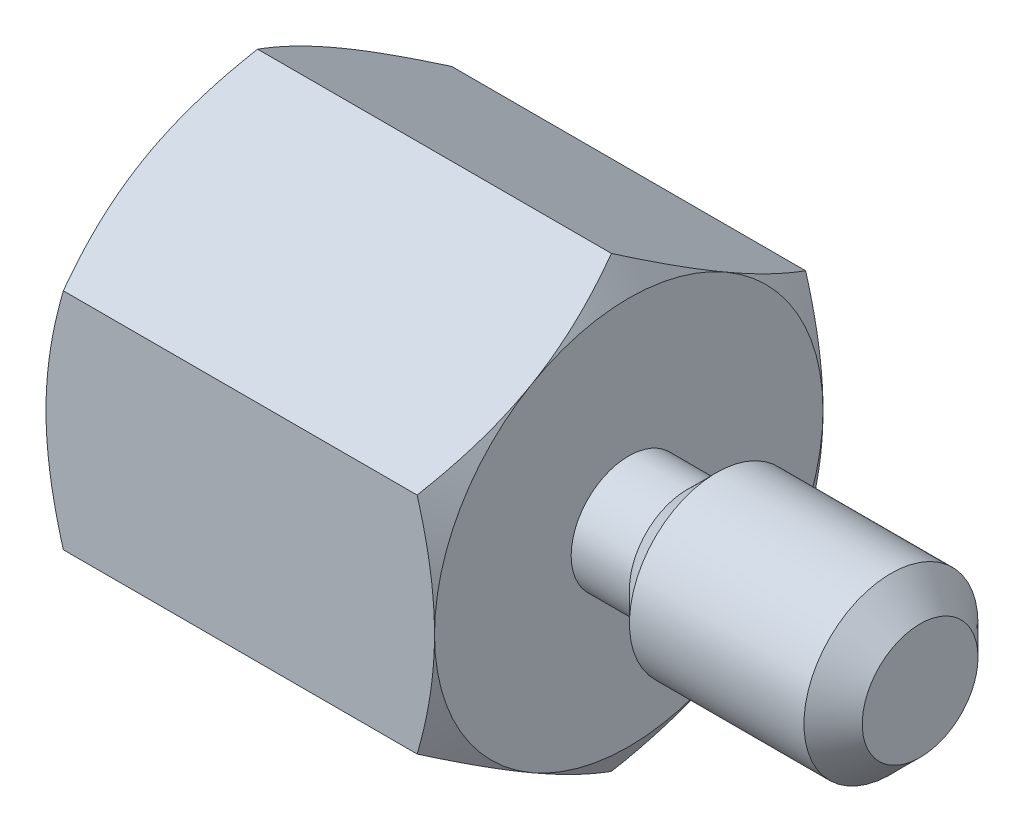
SolidWorks part; units mm, degrees
ref_plane "Front Plane" through (0, 0, 0) normal (0, 0, 1) x (1, 0, 0)
ref_plane "Top Plane" through (0, 0, 0) normal (0, 1, 0) x (1, 0, 0)
ref_plane "Right Plane" through (0, 0, 0) normal (1, 0, 0) x (0, 0, -1)
sketch "Sketch1" plane through (0, 0, 0) normal (0, 0, 1) x (1, 0, 0)
  line L0 (-5.5563, 0) -> (5.5563, 0) construction
  line L1 (5.5563, 1.4224) -> (5.5563, -1.4224) construction
  line L2 (-5.5562, 3.175) -> (-5.5562, -3.175) construction
  line L3 (-2.3813, 1.4224) -> (-2.3813, -1.4224) construction
  line L4 (-2.3813, -1.4224) -> (-5.5563, -1.4224) construction
  line L5 (-2.3813, 1.4224) -> (-5.5563, 1.4224) construction
  line L6 (-5.5562, 3.175) -> (0.7937, 3.175) construction
  line L7 (-5.5562, -3.175) -> (0.7937, -3.175) construction
  line L8 (5.5166, 1.4911) -> (5.8341, 0.9412) construction
  line L9 (5.8341, 0.9412) -> (6.1516, 1.4911) construction
  line L10 (6.1516, 1.4911) -> (5.5166, 1.4911) construction
  line L11 (5.7944, 1.01) -> (5.8738, 1.01) construction
  line L12 (5.5563, 1.4224) -> (6.1119, 1.4224) construction
  line L13 (5.8341, 1.4911) -> (5.8341, 1.4224) construction
  line L14 (5.8341, 1.01) -> (5.8341, 0.9412) construction
  line L15 (5.8341, 1.4568) -> (5.5364, 1.4568) construction
  line L16 (5.8341, 1.4568) -> (6.1317, 1.4568) construction
  point P2 (0.7937, 0)
  point P8 (-2.3813, 0)
  point P13 (3.9688, -1.4224)
  dimension "Hex Size" = 6.35
  dimension "Thread Diameter" = 2.8448
  dimension "D1" = 1.5875
  dimension "Pitch" = 0.635
  dimension "D3" = 0.0794
  dimension "Minimum Thread Length B" = 3.175
  dimension "Thread Length A" = 4.7625
  dimension "Length" = 6.35
ref_plane "Plane1" through (5.5563, 0, 0) normal (1, 0, 0) x (0, 0, -1)
sketch "Sketch2" plane through (5.5563, 0, 0) normal (1, 0, 0) x (0, 0, -1)
  circle A0 centre (0, 0) radius 1.4224
extrude "Extrude1" add sketch "Sketch2" against normal up to vertex (4.7625 mm away) up to point (0.7937, 0, 0)
sketch "Sketch3" [suppressed] plane through (5.5563, 0, 0) normal (1, 0, 0) x (0, 0, -1)
  circle A1 centre (0, 0) radius 1.4224
  circle A2 centre (0, 0) radius 1.4224
  dimension "D1" = 0
chamfer "Chamfer1" distance 0.4763 angle 45 1 edges at (5.5563, 0, -1.4224)
sketch "Sketch4" [suppressed] plane through (0, 0, 0) normal (0, 0, 1) x (1, 0, 0)
  line L1 (5.5364, 1.4568) -> (6.1317, 1.4568)
  line L2 (6.1317, 1.4568) -> (5.8738, 1.01)
  line L3 (5.8738, 1.01) -> (5.7944, 1.01)
  line L4 (5.7944, 1.01) -> (5.5364, 1.4568)
sketch "Sketch16" plane through (0, 0, 0) normal (0, 0, 1) x (1, 0, 0)
  line L0 (0.7937, 0.9412) -> (1.7463, 0.9412)
  line L1 (1.7463, 0.9412) -> (2.2618, 1.4568)
  line L2 (2.2618, 1.4568) -> (0.7937, 1.4568)
  line L3 (0.7937, 1.4568) -> (0.7937, 0.9412)
  line L5 (0, 0) -> (5.5563, 0) construction
  line L6 (5.5563, -0.9462) -> (5.5563, 0.9462) construction
  line L7 (5.8341, 1.4568) -> (5.5364, 1.4568) construction
  dimension "D1" = 0.9525
  dimension "D2" = 45
revolve "Cut-Revolve1" cut sketch "Sketch16" angle 360 about L5
ref_plane "Plane2" through (0.7937, 0, 0) normal (1, 0, 0) x (0, 0, -1)
sketch "Sketch7" plane through (0.7937, 0, 0) normal (1, 0, 0) x (0, 0, -1)
  line L0 (0, 1.4224) -> (0, -1.4224) construction
  line L1 (0, 3.6662) -> (-3.175, 1.8331)
  line L2 (-3.175, 1.8331) -> (-3.175, -1.8331)
  line L3 (-3.175, -1.8331) -> (0, -3.6662)
  line L4 (0, -3.6662) -> (3.175, -1.8331)
  line L5 (3.175, -1.8331) -> (3.175, 1.8331)
  line L6 (3.175, 1.8331) -> (0, 3.6662)
  line L7 (0, 1.4224) -> (0, -1.4224) construction
  line L8 (0.7112, 1.2318) -> (-0.7112, -1.2318) construction
  circle A0 centre (0, 0) radius 3.175 construction
  circle A1 centre (0, 0) radius 1.4224 construction
  point P17 (0, 0)
  point P18 (-0.7112, -1.2318)
  dimension "D1" = 6.35
extrude "Extrude4" add sketch "Sketch7" against normal up to vertex (6.35 mm away) up to point (-5.5563, 0, 0)
sketch "Sketch17" plane through (0, 0, 0) normal (0, 0, 1) x (1, 0, 0)
  line L0 (-5.5563, -3.6662) -> (0.7937, -3.6662) construction
  line L1 (-5.5563, 3.6662) -> (0.7937, 3.6662) construction
  line L2 (-5.5563, -3.6662) -> (0.7937, -3.6662)
  line L3 (-5.5563, 3.6662) -> (0.7937, 3.6662) construction
sketch "Sketch8" plane through (-5.5563, 0, 0) normal (-1, 0, 0) x (0, 0, 1)
  circle A0 centre (0, 0) radius 3.175 construction
  circle A1 centre (0, 0) radius 3.175
extrude "Extrude5" cut sketch "Sketch8" against normal through all draft 60 flip side to cut
sketch "Sketch10" plane through (-5.5563, 0, 0) normal (-1, 0, 0) x (0, 0, 1)
  line L0 (0, 0) -> (-1.0058, 1.0058) construction
  line L1 (0, 0) -> (-1.4224, 0) construction
  circle A0 centre (0, 0) radius 1.4224
  dimension "D1" = 45
extrude "Extrude7" cut sketch "Sketch10" against normal up to vertex (3.175 mm away) up to point (-2.3813, 0, 0)
sketch "Sketch9" plane through (0.7937, 0, 0) normal (1, 0, 0) x (0, 0, -1)
  circle A0 centre (0, 0) radius 3.175 construction
  circle A1 centre (0, 0) radius 3.175
extrude "Extrude6" cut sketch "Sketch9" against normal through all draft 60 flip side to cut
sketch "Sketch11" [suppressed] plane through (-5.5563, 0, 0) normal (-1, 0, 0) x (0, 0, 1)
  circle A0 centre (0, 0) radius 1.4224 construction
  circle A1 centre (0, 0) radius 1.4224
split "Split1" trim tools "Plane2" bodies to split 108 resulting bodies 120 121
chamfer "Chamfer2" distance 0.1588 angle 45 1 edges at (-5.5563, 0, 1.4224)
ref_axis "Center Axis 1" through (-6.6835, 0, 0) along (1, 0, 0)
ref_plane "Contact Plane 1" through (0.7937, 0, 0) normal (1, 0, 0) x (0, 0, -1)
ref_plane "Contact Plane 2" through (-5.5563, 0, 0) normal (-1, 0, 0) x (0, 0, 1)
curve "Helix/Spiral2" [suppressed] pitch 0.635 height 3.81 turns 6 parameters "Female Pitch"=0.635
sketch "Sketch12" [suppressed] plane through (0, 0, 0) normal (0, 0, 1) x (1, 0, 0)
  line L0 (-6.1516, 1.4911) -> (-5.8341, 0.9412) construction
  line L1 (-5.8341, 0.9412) -> (-5.5166, 1.4911) construction
  line L2 (-5.5166, 1.4911) -> (-6.1516, 1.4911) construction
  line L3 (-6.1119, 1.4224) -> (-5.5563, 1.4224) construction
  line L4 (-5.8738, 1.01) -> (-5.7944, 1.01) construction
  line L6 (-5.8341, 1.01) -> (-5.8341, 0.9412) construction
  line L7 (-5.8341, 1.4911) -> (-5.8341, 1.4224) construction
  line L8 (-5.8341, 1.4568) -> (-6.1317, 1.4568)
  line L9 (-5.8341, 1.4568) -> (-5.5364, 1.4568)
  line L10 (-6.1317, 1.4568) -> (-5.8738, 1.01)
  line L11 (-5.8738, 1.01) -> (-5.7944, 1.01)
  line L12 (-5.7944, 1.01) -> (-5.5364, 1.4568)
  dimension "Female Pitch" = 0.635
  dimension "D1" = 0.0794
sweep "Sweep3" [suppressed] add profiles "Sketch12" path "Helix/Spiral2"
curve "Helix/Spiral3" [suppressed] pitch 0.635 height 5.3975 turns 8.5
sweep "Cut-Sweep1" [suppressed] cut profiles "Sketch4" path "Helix/Spiral3"
sketch "Sketch18" [suppressed] plane through (-5.5563, 0, 0) normal (-1, 0, 0) x (0, 0, 1)
  circle A0 centre (0, 0) radius 1.5811 construction
  circle A1 centre (0, 0) radius 1.5812
extrude "Cut-Extrude1" [suppressed] cut sketch "Sketch18" against normal through all draft 45 and the other way through all draft 45
combine bodies "Combine1" [suppressed] operation type add bodies to combine 119 124
equation "\"D3@Helix/Spiral2\"=\"Minimum Thread Length B@Sketch1\" +  ( \"Pitch@Sketch1\" )"
equation "\"D1@Sketch1\"=\"Pitch@Sketch1\" * 2.5"
equation "\"D3@Sketch1\" = \"Pitch@Sketch1\" / 8"
equation "\"D4@Helix/Spiral3\" = \"Pitch@Sketch1\""
equation "\"D3@Helix/Spiral3\" = \"Pitch@Sketch1\" + \"Thread Length A@Sketch1\""
equation "\"D1@Chamfer1\" = \"Pitch@Sketch1\" * .75"
equation "\"Female Pitch@Sketch12\" = \"Pitch@Sketch1\""
equation "\"D1@Sketch12\"=\"Female Pitch@Sketch12\"/8"
equation "\"D1@Sketch16\" = \"Pitch@Sketch1\" * 1.5"
equation "\"D1@Chamfer2\" = \"Pitch@Sketch1\" * .25"
